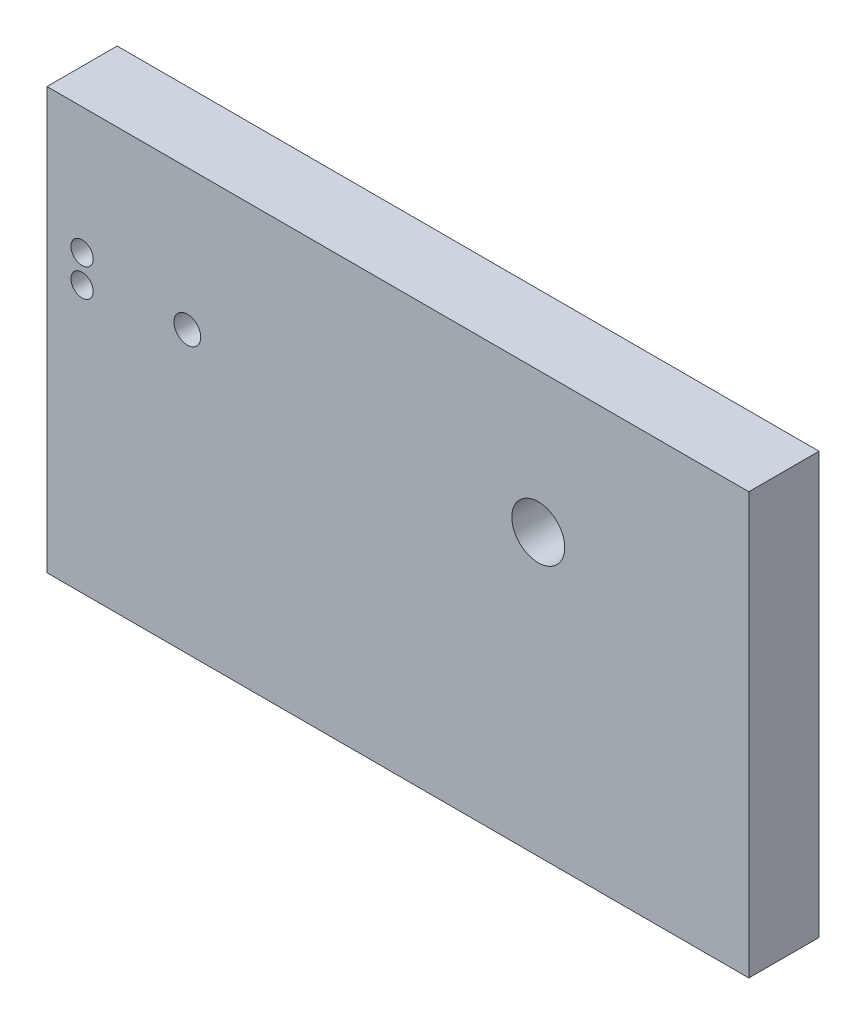
SolidWorks part; units mm, degrees
ref_plane "Front Plane" through (0, 0, 0) normal (0, 0, 1) x (1, 0, 0)
ref_plane "Top Plane" through (0, 0, 0) normal (0, 1, 0) x (1, 0, 0)
ref_plane "Right Plane" through (0, 0, 0) normal (1, 0, 0) x (0, 0, -1)
sketch "Sketch1" plane through (0, 0, 0) normal (0, 0, 1) x (1, 0, 0)
  line L1 (0, 0) -> (127, 0)
  line L2 (0, 0) -> (0, 76.2)
  line L3 (0, 76.2) -> (127, 76.2)
  line L4 (127, 0) -> (127, 76.2)
  dimension "D1" = 127
  dimension "D2" = 76.2
extrude "Boss-Extrude1" add sketch "Sketch1" along normal blind 12.7 contours L2 L1 L4 L3
hole_wizard "#11 (0.191) Diameter Hole1" positions "Sketch5" profile "Sketch6" hole size "#11" standard "ANSI Inch" end condition through all
sketch "Sketch5" plane through (0, 0, 12.7) normal (0, 0, 1) x (1, 0, 0)
  line L0 (0, 0) -> (0, 76.2) construction
  line L1 (0, 0) -> (127, 0) construction
  point P0 (25.4, 50.8)
  dimension "D1" = 25.4
  dimension "D2" = 50.8
sketch "Sketch6" plane through (25.4, 50.8, 12.7) normal (1, 0, 0) x (0, -1, 0)
  line L0 (0, 0) -> (0, 12.7)
  line L1 (0, 12.7) -> (2.4257, 12.7)
  line L2 (2.4257, 12.7) -> (2.4257, 0)
  line L5 (2.4257, 0) -> (0, 0)
  line L11 (0, -6.35) -> (0, 107.95) construction
  dimension "Thru Hole Dia." = 4.8514
  dimension "Thru Hole Depth" = 12.7
hole_wizard "#10-32 Tapped Hole1" positions "Sketch9" profile "Sketch10" tap size "#10-32" standard "ANSI Inch"
sketch "Sketch9" plane through (0, 0, 0) normal (0, -1, 0) x (-1, 0, 0)
  line L0 (0, -12.7) -> (-127, -12.7) construction
  line L1 (-19.05, -6.35) -> (-107.95, -6.35) construction
  line L3 (-63.5, -12.7) -> (-63.5, 0) construction
  line L4 (0, 0) -> (-127, 0) construction
  point P0 (-19.05, -6.35)
  point P2 (-107.95, -6.35)
  point P21 (-63.5, -6.35)
  dimension "D1" = 6.35
  dimension "D2" = 88.9
sketch "Sketch10" plane through (19.05, 0, 6.35) normal (1, 0, 0) x (0, 0, -1)
  line L0 (0, 0) -> (0, 13.9133)
  line L1 (0, 13.9133) -> (2.0193, 12.7)
  line L2 (2.0193, 12.7) -> (2.0193, 0)
  line L5 (2.0193, 0) -> (0, 0)
  line L10 (0, 13.9133) -> (-2.0193, 12.7) construction
  line L11 (0, -6.35) -> (0, 107.95) construction
  dimension "Tap Drill Dia." = 4.0386
  dimension "Tap Drill Depth" = 12.7
  dimension "Drill Angle" = 118
cosmetic thread "Hole Thread3" parameters "D1"=12.7, "D2"=4.826
cosmetic thread "Hole Thread4" parameters "D1"=12.7, "D2"=4.826
hole_wizard "V (0.377) Diameter Hole1" positions "Sketch14" profile "Sketch15" hole size "V" standard "ANSI Inch" end condition through all
sketch "Sketch14" plane through (0, 0, 12.7) normal (0, 0, 1) x (1, 0, 0)
  line L0 (0, 0) -> (127, 0) construction
  line L1 (0, 0) -> (0, 76.2) construction
  point P0 (88.9, 50.8)
  dimension "D1" = 50.8
  dimension "D2" = 88.9
sketch "Sketch15" plane through (88.9, 50.8, 12.7) normal (1, 0, 0) x (0, -1, 0)
  line L0 (0, 0) -> (0, 12.7)
  line L1 (0, 12.7) -> (4.7879, 12.7)
  line L2 (4.7879, 12.7) -> (4.7879, 0)
  line L5 (4.7879, 0) -> (0, 0)
  line L11 (0, -6.35) -> (0, 107.95) construction
  dimension "Thru Hole Dia." = 9.5758
  dimension "Thru Hole Depth" = 12.7
hole_wizard "#10-32 Tapped Hole2" positions "Sketch16" profile "Sketch17" tap size "#10-32" standard "ANSI Inch" end condition through all
sketch "Sketch16" plane through (0, 0, 12.7) normal (0, 0, 1) x (1, 0, 0)
  line L0 (0, 0) -> (0, 76.2) construction
  line L1 (0, 0) -> (127, 0) construction
  point P0 (6.35, 48.26)
  dimension "D1" = 6.35
  dimension "D2" = 48.26
cosmetic thread "Hole Thread5" parameters "D2"=4.826
sketch "Sketch17" plane through (6.35, 48.26, 12.7) normal (1, 0, 0) x (0, -1, 0)
  line L0 (0, 0) -> (0, 12.7)
  line L1 (0, 12.7) -> (2.0193, 12.7)
  line L2 (2.0193, 12.7) -> (2.0193, 0)
  line L5 (2.0193, 0) -> (0, 0)
  line L11 (0, -6.35) -> (0, 107.95) construction
  dimension "Thru Tap Drill Dia." = 4.0386
  dimension "Thru Tap Drill Depth" = 12.7
hole_wizard "#21 (0.159) Diameter Hole1" positions "Sketch18" profile "Sketch19" hole size "#21" standard "ANSI Inch" end condition through all
sketch "Sketch18" plane through (0, 0, 12.7) normal (0, 0, 1) x (1, 0, 0)
  line L0 (0, 0) -> (0, 76.2) construction
  line L1 (0, 0) -> (127, 0) construction
  point P0 (6.35, 53.34)
  dimension "D1" = 6.35
  dimension "D2" = 53.34
sketch "Sketch19" plane through (6.35, 53.34, 12.7) normal (1, 0, 0) x (0, -1, 0)
  line L0 (0, 0) -> (0, 12.7)
  line L1 (0, 12.7) -> (2.0193, 12.7)
  line L2 (2.0193, 12.7) -> (2.0193, 0)
  line L5 (2.0193, 0) -> (0, 0)
  line L11 (0, -6.35) -> (0, 107.95) construction
  dimension "Thru Hole Dia." = 4.0386
  dimension "Thru Hole Depth" = 12.7
